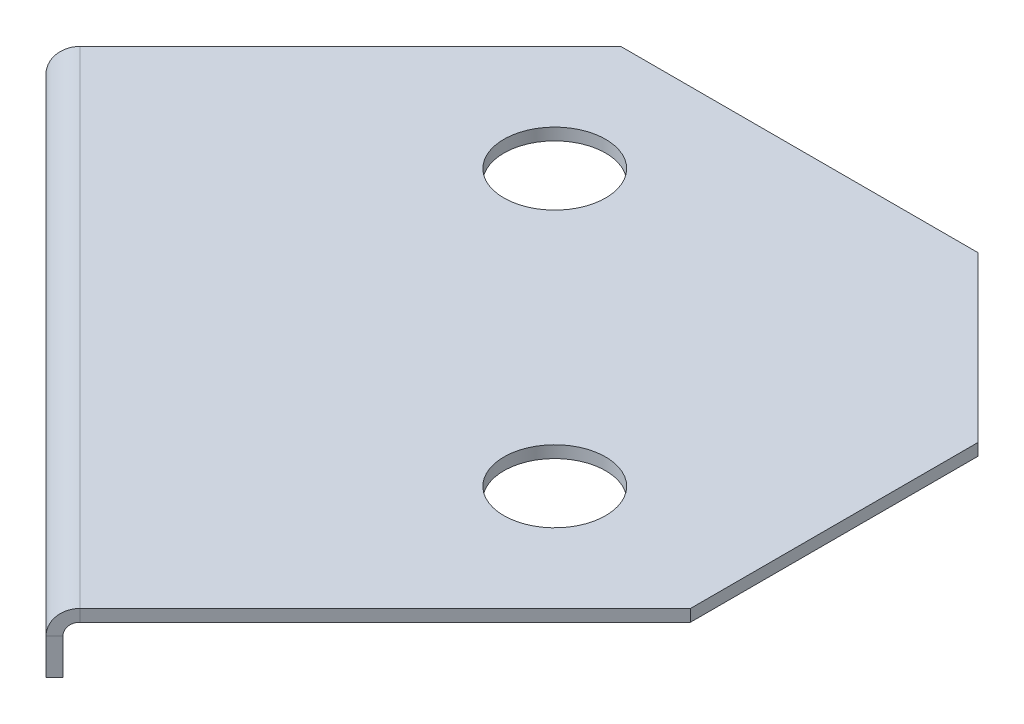
SolidWorks part; units mm, degrees
note: The reader was unsure of these and kept them because the rebuilt part matched: flange length of "Edge-Flange1".
ref_plane "Front Plane" through (0, 0, 0) normal (0, 0, 1) x (1, 0, 0)
ref_plane "Top Plane" through (0, 0, 0) normal (0, 1, 0) x (1, 0, 0)
ref_plane "Right Plane" through (0, 0, 0) normal (1, 0, 0) x (0, 0, -1)
sketch "Sketch1" plane through (0, 0, 0) normal (0, 1, 0) x (1, 0, 0)
  line L0 (-3.1059, 7.9526) -> (5.7329, -0.8862) construction
  line L1 (3.6116, -3.0076) -> (3.6116, -8.4601) construction
  line L2 (3.6116, -8.4601) -> (8.5, -8.4601) construction
  line L3 (8.5, -8.4601) -> (8.5, 10.1379) construction
  line L4 (8.5, 10.1379) -> (-8.5, 10.1379) construction
  line L5 (-8.5, 10.1379) -> (-8.5, 5.8313) construction
  line L6 (-8.5, 5.8313) -> (-5.2272, 5.8313) construction
  line L7 (-5.2272, 5.8313) -> (3.6116, -3.0076) construction
  line L8 (5.754, 10.1379) -> (-0.2134, 10.1379)
  line L9 (-0.2134, 10.1379) -> (-4.8737, 5.4777)
  line L10 (-4.8737, 5.4777) -> (3.2581, -2.654)
  line L11 (3.2581, -2.654) -> (8.5, 2.5879)
  line L12 (8.5, 2.5879) -> (8.5, 7.3919)
  line L13 (8.5, 7.3919) -> (5.754, 10.1379)
  arc A0 (-3.1059, 7.9526) -> (-5.2272, 5.8313) centre (-4.1665, 6.8919) ccw construction
  arc A1 (3.6116, -3.0076) -> (5.7329, -0.8862) centre (4.6723, -1.9469) ccw construction
  dimension "D5" = 1.5
  dimension "D6" = 1.5
  dimension "D1" = 4.3067
  dimension "D2" = 17
  dimension "D3" = 18.598
  dimension "D4" = 4.8884
  dimension "D7" = 3.2728
  dimension "D8" = 5.4525
  dimension "D9" = 45
  dimension "D10" = 0.5
  dimension "D11" = 0.5
base flange "Base-Flange1" sketch "Sketch1" thickness 0.2 reverse thickness direction no parameters "D1"=1.5
edge flange "Edge-Flange1" sketch "Sketch8" flange angle 90 flange length 1 flange position material outside bend radius 0.2 thickness 0.2 relief rectangular parameters "D6"=10
sketch "Sketch8" plane through (0.302, -0.2, -0.302) normal (-0.7071, 0, 0.7071) x (-0.7071, 0, -0.7071)
  line L2 (-4.1805, 0) -> (-4.1805, 0.8)
  line L3 (-4.1805, 0.8) -> (7.3195, 0.8)
  line L4 (7.3195, 0.8) -> (7.3195, 0)
  line L7 (7.3195, 0) -> (-4.1805, 0) construction
  line L8 (7.3195, 0) -> (-4.1805, 0)
bend "EdgeBend1" bend radius 0.2 bend angle 90 parameters "D5"=1
hole_wizard "Ø1.7 (1.7) Diameter Hole1" positions "Sketch9" profile "Sketch10" hole size "Ø1.7" standard "ANSI Metric" end condition up to next
sketch "Sketch9" plane through (0, 0, 0) normal (0, 1, 0) x (1, 0, 0)
  line L0 (-0.2134, 10.1379) -> (-4.7322, 5.6191) construction
  line L1 (3.3995, -2.5126) -> (8.5, 2.5879) construction
  line L2 (8.5, 7.3919) -> (5.754, 10.1379) construction
  point P0 (1.0025, 7.8184)
  point P2 (5.5987, 3.2222)
  dimension "D1" = 2.5
  dimension "D2" = 2.5
  dimension "D3" = 5
  dimension "D4" = 5
sketch "Sketch10" plane through (1.0025, 0, -7.8184) normal (1, 0, 0) x (0, 0, 1)
  line L0 (0, 0) -> (0, 0.2)
  line L1 (0, 0.2) -> (0.85, 0.2)
  line L2 (0.85, 0.2) -> (0.85, 0)
  line L5 (0.85, 0) -> (0, 0)
  line L11 (0, -6.35) -> (0, 107.95) construction
  dimension "Thru Hole Dia." = 1.7
  dimension "Thru Hole Depth" = 0.2
sketch "Bend-Lines1" [suppressed] plane through (0, 0, 0) normal (0, 1, 0) x (1, 0, 0)
sketch "Bounding-Box1" [suppressed] plane through (0, 0, 0) normal (0, 1, 0) x (1, 0, 0)
sheet metal parameters "Sheet-Metal1" thickness 0.2 parameters "D1"=1.5
flat pattern "Flat-Pattern1" [suppressed]
sketch "Bend-Lines2" plane through (0, 0, 0) normal (0, 1, 0) x (1, 0, 0)
sketch3d "Bounding-Box2" [suppressed]
  line L0 (4.8737, 5.4777, 0) -> (-3.2581, -2.654, 0) construction
  line L1 (-2.7703, 13.1217, 0) -> (-10.902, 4.9899, 0) construction
  line L2 (4.8737, 5.4777, 0) -> (-2.7703, 13.1217, 0) construction
  line L3 (-3.2581, -2.654, 0) -> (-10.902, 4.9899, 0) construction
sheet metal parameters "Sheet-Metal2" thickness 0.2 parameters "D1"=1.5
flat pattern "Flat-Pattern1"
sketch "Bend-Lines2" plane through (0, 0, 0) normal (0, 1, 0) x (1, 0, 0)
  line L0 (-4.8988, 5.4525) -> (3.2329, -2.6792) construction
  line L1 (-4.8988, 5.4525) -> (3.2329, -2.6792) construction
sketch3d "Bounding-Box2" [suppressed]
  line L0 (10.902, 4.9899, 0) -> (2.642, -3.2701, 0) construction
  line L1 (2.7703, 13.1217, 0) -> (-5.4897, 4.8617, 0) construction
  line L2 (10.902, 4.9899, 0) -> (2.7703, 13.1217, 0) construction
  line L3 (2.642, -3.2701, 0) -> (-5.4897, 4.8617, 0) construction
bend of the flat pattern "Flatten-<EdgeBend1>1"
sheet metal parameters "Sheet-Metal3" thickness 0.2 parameters "D1"=1.5
flat pattern "Flat-Pattern1"
sketch "Bend-Lines2" plane through (0, 0, 0) normal (0, 1, 0) x (1, 0, 0)
  line L0 (-4.8988, 5.4525) -> (3.2329, -2.6792) construction
  line L1 (-4.8988, 5.4525) -> (3.2329, -2.6792) construction
sketch3d "Bounding-Box2" [suppressed]
  line L0 (10.902, 4.9899, 0) -> (2.642, -3.2701, 0) construction
  line L1 (2.7703, 13.1217, 0) -> (-5.4897, 4.8617, 0) construction
  line L2 (10.902, 4.9899, 0) -> (2.7703, 13.1217, 0) construction
  line L3 (2.642, -3.2701, 0) -> (-5.4897, 4.8617, 0) construction
bend of the flat pattern "Flatten-<EdgeBend1>1"
